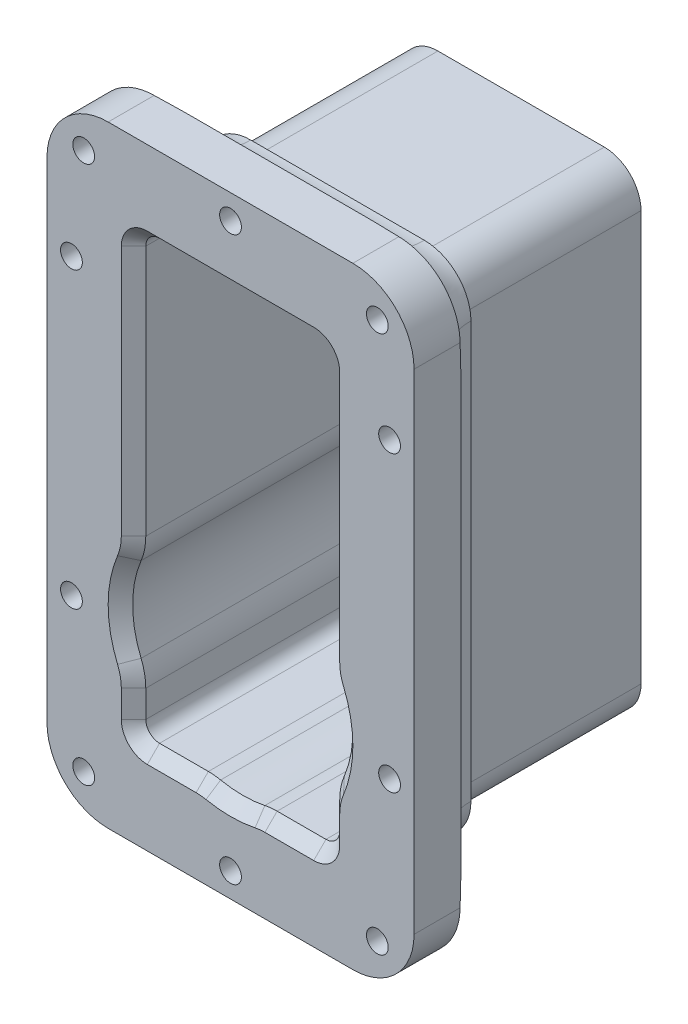
SolidWorks part; units mm, degrees
material "6061-T6 (SS)"
ref_plane "Front Plane" through (0, 0, 0) normal (0, 0, 1) x (1, 0, 0)
ref_plane "Top Plane" through (0, 0, 0) normal (0, 1, 0) x (1, 0, 0)
ref_plane "Right Plane" through (0, 0, 0) normal (1, 0, 0) x (0, 0, -1)
sketch "Sketch1" plane through (0, 0, 0) normal (0, 0, 1) x (1, 0, 0)
  line L1 (-19.05, -31.75) -> (19.05, -31.75)
  line L2 (-19.05, -31.75) -> (-19.05, 31.75)
  line L3 (-19.05, 31.75) -> (19.05, 31.75)
  line L4 (19.05, -31.75) -> (19.05, 31.75)
  line L5 (-19.05, -31.75) -> (19.05, 31.75) construction
  line L6 (-19.05, 31.75) -> (19.05, -31.75) construction
  point P0 (0, 0)
  dimension "D1" = 63.5
  dimension "D2" = 38.1
extrude "Boss-Extrude1" add sketch "Sketch1" along normal mid plane 4.7625
sketch "Sketch2" plane through (0, 0, -2.3813) normal (0, 0, -1) x (-1, 0, 0)
  line L1 (-12.446, -25.0825) -> (12.446, -25.0825)
  line L2 (-12.446, -25.0825) -> (-12.446, 25.0825)
  line L3 (-12.446, 25.0825) -> (12.446, 25.0825)
  line L4 (12.446, -25.0825) -> (12.446, 25.0825)
  line L5 (-12.446, -25.0825) -> (12.446, 25.0825) construction
  line L6 (-12.446, 25.0825) -> (12.446, -25.0825) construction
  point P0 (0, 0)
  dimension "D1" = 24.892
  dimension "D2" = 50.165
extrude "Boss-Extrude2" add sketch "Sketch2" along normal blind 25.4
fillet "Fillet1" radius 3.81 4 edges at (12.446, -25.0825, -15.0813) (-12.446, -25.0825, -15.0813) (-12.446, 25.0825, -15.0813) (12.446, 25.0825, -15.0813)
fillet "Fillet2" radius 6.35 4 edges at (19.05, 31.75, 0) (-19.05, 31.75, 0) (-19.05, -31.75, 0) (19.05, -31.75, 0)
sketch "Sketch3" plane through (0, 0, -2.3813) normal (0, 0, -1) x (-1, 0, 0)
  line L5 (-13.843, -26.416) -> (13.843, -26.416)
  line L6 (-13.843, -26.416) -> (-13.843, 26.416)
  line L7 (-13.843, 26.416) -> (13.843, 26.416)
  line L8 (13.843, -26.416) -> (13.843, 26.416)
  line L9 (-13.843, -26.416) -> (13.843, 26.416) construction
  line L10 (-13.843, 26.416) -> (13.843, -26.416) construction
  point P0 (0, 0)
  dimension "D1" = 52.832
  dimension "D2" = 27.686
extrude "Boss-Extrude3" add sketch "Sketch3" along normal blind 6.35
fillet "Fillet3" radius 4.826 4 edges at (-13.843, -26.416, -5.5562) (13.843, -26.416, -5.5562) (13.843, 26.416, -5.5562) (-13.843, 26.416, -5.5562)
fillet "Fillet4" radius 6.35 8 edges at (-12.4295, 25.0025, -2.3813) (-12.4295, -25.0025, -2.3813) (12.4295, -25.0025, -2.3813) (12.4295, 25.0025, -2.3813) (-13.843, 0, -2.3813) (0, -26.416, -2.3813) (13.843, 0, -2.3813) (0, 26.416, -2.3813)
sketch "Sketch4" plane through (0, 0, -27.7812) normal (0, 0, -1) x (-1, 0, 0)
  line L8 (-10.0647, 21.2725) -> (-10.0647, -21.2725)
  line L9 (-8.636, -22.7012) -> (8.636, -22.7012)
  line L10 (10.0647, -21.2725) -> (10.0647, 21.2725)
  line L11 (8.636, 22.7012) -> (-8.636, 22.7012)
  line L12 (-10.0647, 21.2725) -> (-10.0647, -21.2725)
  line L13 (-8.636, -22.7012) -> (8.636, -22.7012)
  line L14 (10.0647, -21.2725) -> (10.0647, 21.2725)
  line L15 (8.636, 22.7012) -> (-8.636, 22.7012)
  arc A8 (-10.0647, -21.2725) -> (-8.636, -22.7012) centre (-8.636, -21.2725) ccw
  arc A9 (8.636, -22.7012) -> (10.0647, -21.2725) centre (8.636, -21.2725) ccw
  arc A10 (10.0647, 21.2725) -> (8.636, 22.7012) centre (8.636, 21.2725) ccw
  arc A11 (-8.636, 22.7012) -> (-10.0647, 21.2725) centre (-8.636, 21.2725) ccw
  arc A12 (-10.0647, -21.2725) -> (-8.636, -22.7012) centre (-8.636, -21.2725) ccw
  arc A13 (8.636, -22.7012) -> (10.0647, -21.2725) centre (8.636, -21.2725) ccw
  arc A14 (10.0647, 21.2725) -> (8.636, 22.7012) centre (8.636, 21.2725) ccw
  arc A15 (-8.636, 22.7012) -> (-10.0647, 21.2725) centre (-8.636, 21.2725) ccw
  dimension "D1" = 2.3813
extrude "Cut-Extrude1" cut sketch "Sketch4" against normal up to next
hole_wizard "#4-40 Tapped Hole1" positions "Sketch8" profile "Sketch7" tap size "#4-40" standard "Ansi Inch"
sketch "Sketch8" plane through (0, 0, 2.3813) normal (0, 0, 1) x (1, 0, 0)
  line L0 (-9.6463, -22.2828) -> (-17.1901, -29.8901) construction
  line L2 (-9.6463, 22.2828) -> (-17.1901, 29.8901) construction
  line L4 (9.6463, 22.2828) -> (17.1901, 29.8901) construction
  line L10 (-19.05, 25.4) -> (-19.05, -25.4) construction
  line L11 (19.05, -25.4) -> (19.05, 25.4) construction
  line L12 (12.7, 31.75) -> (-12.7, 31.75) construction
  line L13 (-12.7, -31.75) -> (12.7, -31.75) construction
  arc A0 (-10.0647, -21.2725) -> (-8.636, -22.7012) centre (-8.636, -21.2725) ccw construction
  arc A1 (-19.05, -25.4) -> (-12.7, -31.75) centre (-12.7, -25.4) ccw construction
  arc A2 (-8.636, 22.7012) -> (-10.0647, 21.2725) centre (-8.636, 21.2725) ccw construction
  arc A3 (-12.7, 31.75) -> (-19.05, 25.4) centre (-12.7, 25.4) ccw construction
  arc A4 (10.0647, 21.2725) -> (8.636, 22.7012) centre (8.636, 21.2725) ccw construction
  arc A5 (19.05, 25.4) -> (12.7, 31.75) centre (12.7, 25.4) ccw construction
  point P0 (-15.24, 27.9236)
  point P1 (15.24, 27.9236)
  point P7 (-15.24, -27.9236)
  point P9 (15.24, -27.9236)
  point P56 (-16.51, 17.78)
  point P58 (-16.51, -12.7)
  point P60 (16.51, 17.78)
  point P62 (16.51, -12.7)
  point P92 (0, 29.21)
  point P94 (0, -29.21)
  dimension "D1" = 15.24
  dimension "D2" = 2.54
  dimension "D3" = 2.54
  dimension "D4" = 2.54
  dimension "D5" = 2.54
  dimension "D6" = 30.48
  dimension "D7" = 17.78
sketch "Sketch7" plane through (-15.24, 27.9236, 2.3813) normal (1, 0, 0) x (0, -1, 0)
  line L0 (0, 0) -> (0, 8.2992)
  line L1 (0, 8.2992) -> (1.1303, 7.62)
  line L2 (1.1303, 7.62) -> (1.1303, 0)
  line L5 (1.1303, 0) -> (0, 0)
  line L10 (0, 8.2992) -> (-1.1303, 7.62) construction
  line L11 (0, -6.35) -> (0, 107.95) construction
  dimension "Tap Drill Dia." = 2.2606
  dimension "Tap Drill Depth" = 7.62
  dimension "Drill Angle" = 118
cosmetic thread "Hole Thread1" parameters "D1"=5.588, "D2"=2.8448
cosmetic thread "Hole Thread2" parameters "D1"=5.588, "D2"=2.8448
cosmetic thread "Hole Thread5" parameters "D1"=5.588, "D2"=2.8448
cosmetic thread "Hole Thread6" parameters "D1"=5.588, "D2"=2.8448
cosmetic thread "Hole Thread8" parameters "D1"=5.588, "D2"=2.8448
cosmetic thread "Hole Thread9" parameters "D1"=5.588, "D2"=2.8448
cosmetic thread "Hole Thread10" parameters "D1"=5.588, "D2"=2.8448
cosmetic thread "Hole Thread11" parameters "D1"=5.588, "D2"=2.8448
cosmetic thread "Hole Thread13" parameters "D1"=5.588, "D2"=2.8448
cosmetic thread "Hole Thread14" parameters "D1"=5.588, "D2"=2.8448
sketch "Sketch9" plane through (0, 0, 2.3813) normal (0, 0, 1) x (1, 0, 0)
  line L1 (-12.7, -31.75) -> (12.7, -31.75) construction
  circle A0 centre (0, -11.6332) radius 11.43
  dimension "D2" = 22.86
  dimension "D1" = 20.1168
extrude "Cut-Extrude2" cut sketch "Sketch9" against normal through all
fillet "Fillet5" radius 6.35 6 edges at (10.0647, -17.0504, -12.7) (10.0647, -6.216, -12.7) (-10.0647, -17.0504, -12.7) (-10.0647, -6.216, -12.7) (2.8536, -22.7012, -12.7) (-2.8536, -22.7012, -12.7)
chamfer "Chamfer1" distance 1.27 angle 45 19 edges at (9.6463, -22.2828, 2.3813) (-9.6463, -22.2828, 2.3813) (10.0647, -19.8691, 2.3813) (-10.0647, -19.8691, 2.3813) (10.1878, -17.2216, 2.3813) (-10.1878, -17.2216, 2.3813) (11.43, -11.6332, 2.3813) (-11.43, -11.6332, 2.3813) (10.1878, -6.0448, 2.3813) (-10.1878, -6.0448, 2.3813) (10.0647, 8.2359, 2.3813) (-10.0647, 8.2359, 2.3813) (9.6463, 22.2828, 2.3813) (-9.6463, 22.2828, 2.3813) (0, 22.7012, 2.3813) (0, -23.0632, 2.3813) (2.9287, -22.7336, 2.3813) (-2.9287, -22.7336, 2.3813) (6.1027, -22.7012, 2.3813)
